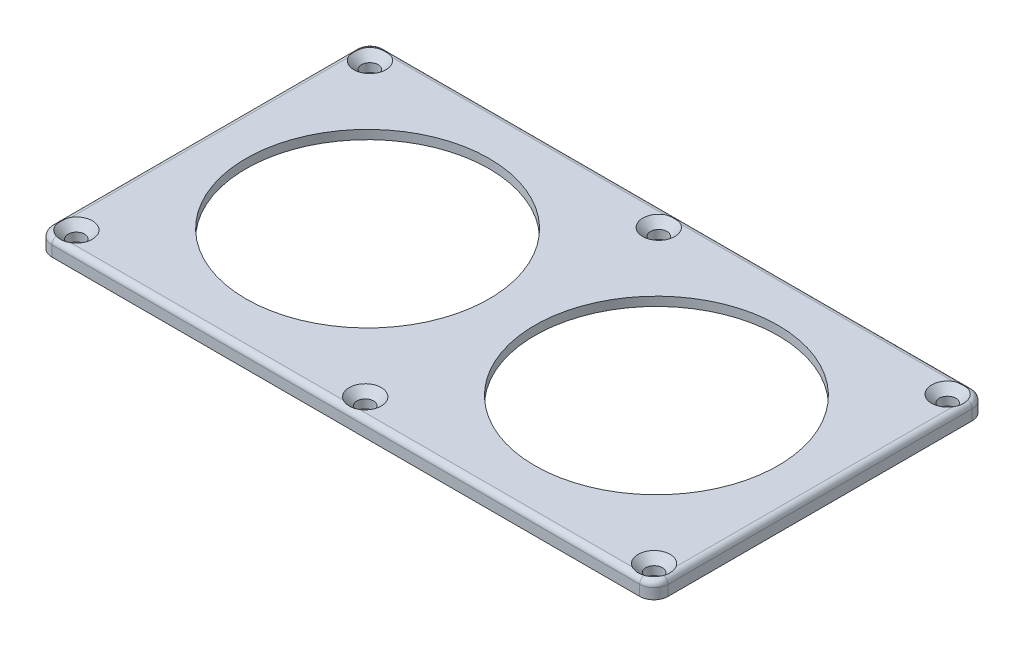
SolidWorks part; units mm, degrees
ref_plane "Front Plane" through (0, 0, 0) normal (0, 0, 1) x (1, 0, 0)
ref_plane "Top Plane" through (0, 0, 0) normal (0, 1, 0) x (1, 0, 0)
ref_plane "Right Plane" through (0, 0, 0) normal (1, 0, 0) x (0, 0, -1)
sketch "Sketch1" plane through (0, 0, 0) normal (0, 1, 0) x (1, 0, 0)
  line L1 (72.5, -41) -> (-72.5, -41)
  line L2 (76, -37.5) -> (76, 37.5)
  line L3 (72.5, 41) -> (-72.5, 41)
  line L4 (-76, -37.5) -> (-76, 37.5)
  line L5 (76, -41) -> (-76, 41) construction
  line L6 (76, 41) -> (-76, -41) construction
  line L7 (71.25, -36.2) -> (-71.25, -36.2) construction
  line L8 (71.25, -36.2) -> (71.25, 36.2) construction
  line L9 (71.25, 36.2) -> (-71.25, 36.2) construction
  line L10 (-71.25, -36.2) -> (-71.25, 36.2) construction
  line L11 (71.25, -36.2) -> (-71.25, 36.2) construction
  line L12 (71.25, 36.2) -> (-71.25, -36.2) construction
  circle A0 centre (-71.25, 36.2) radius 2.05
  circle A1 centre (-71.25, -36.2) radius 2.05
  circle A2 centre (71.25, -36.2) radius 2.05
  circle A3 centre (71.25, 36.2) radius 2.05
  arc A4 (-72.5, -41) -> (-76, -37.5) centre (-72.5, -37.5) cw
  arc A5 (72.5, -41) -> (76, -37.5) centre (72.5, -37.5) ccw
  arc A6 (76, 37.5) -> (72.5, 41) centre (72.5, 37.5) ccw
  arc A7 (-72.5, 41) -> (-76, 37.5) centre (-72.5, 37.5) ccw
  circle A8 centre (0, 36.2) radius 2.05
  circle A9 centre (0, -36.2) radius 2.05
  point P0 (0, 0)
  point P6 (0, 0)
  dimension "D5" = 4.1
  dimension "D6" = 3.5
  dimension "D1" = 152
  dimension "D2" = 82
  dimension "D3" = 72.4
  dimension "D4" = 142.5
extrude "Boss-Extrude1" add sketch "Sketch1" along normal blind 4
fillet "Fillet1" radius 1.4 8 edges at (-74.9749, 4, 39.9749) (-76, 4, 0) (-74.9749, 4, -39.9749) (0, 4, -41) (74.9749, 4, -39.9749) (76, 4, 0) (74.9749, 4, 39.9749) (0, 4, 41)
chamfer "Chamfer1" distance 1.9 angle 45 6 edges at (71.25, 4, 38.25) (71.25, 4, -34.15) (-71.25, 4, 38.25) (-71.25, 4, -34.15) (0, 4, 38.25) (0, 4, -34.15)
sketch "Sketch2" plane through (0, 0, 0) normal (0, -1, 0) x (1, 0, 0)
  line L5 (-71.25, 33.35) -> (-72.5, 33.35)
  line L6 (-72.5, -33.35) -> (-72.5, 33.35)
  line L20 (-71.25, -33.35) -> (-72.5, -33.35)
  line L21 (-68.4, -36.2) -> (-68.4, -37.45)
  line L22 (-2.85, -37.45) -> (-68.4, -37.45)
  line L23 (-2.85, -36.2) -> (-2.85, -37.45)
  line L24 (2.85, -36.2) -> (2.85, -37.45)
  line L25 (68.4, -37.45) -> (2.85, -37.45)
  line L26 (68.4, -36.2) -> (68.4, -37.45)
  line L27 (71.25, -33.35) -> (72.5, -33.35)
  line L28 (72.5, -33.35) -> (72.5, 33.35)
  line L29 (71.25, 33.35) -> (72.5, 33.35)
  line L30 (68.4, 36.2) -> (68.4, 37.45)
  line L31 (68.4, 37.45) -> (2.85, 37.45)
  line L32 (2.85, 36.2) -> (2.85, 37.45)
  line L33 (-2.85, 36.2) -> (-2.85, 37.45)
  line L34 (-2.85, 37.45) -> (-68.4, 37.45)
  line L35 (-68.4, 36.2) -> (-68.4, 37.45)
  arc A12 (-71.25, -33.35) -> (-68.4, -36.2) centre (-71.25, -36.2) cw
  arc A13 (-2.85, -36.2) -> (2.85, -36.2) centre (0, -36.2) cw
  arc A14 (68.4, -36.2) -> (71.25, -33.35) centre (71.25, -36.2) cw
  arc A15 (68.4, 36.2) -> (71.25, 33.35) centre (71.25, 36.2) ccw
  arc A16 (-2.85, 36.2) -> (2.85, 36.2) centre (0, 36.2) ccw
  arc A17 (-71.25, 33.35) -> (-68.4, 36.2) centre (-71.25, 36.2) ccw
  point P0 (0, 0)
extrude "Cut-Extrude1" cut sketch "Sketch2" against normal blind 1.8
sketch "Sketch3" plane through (0, 4, 0) normal (0, 1, 0) x (1, 0, 0)
  point P0 (0, 0)
sketch "Sketch4" plane through (0, 4, 0) normal (0, 1, 0) x (1, 0, 0)
  line L0 (0, 0) -> (-51.5573, 0) construction
  line L1 (0, 0) -> (63.3788, 0) construction
  circle A0 centre (-35.625, 0) radius 30
  circle A1 centre (35.625, 0) radius 30
  dimension "D3" = 60
  dimension "D1" = 35.625
  dimension "D2" = 35.625
extrude "Cut-Extrude2" cut sketch "Sketch4" against normal through all
